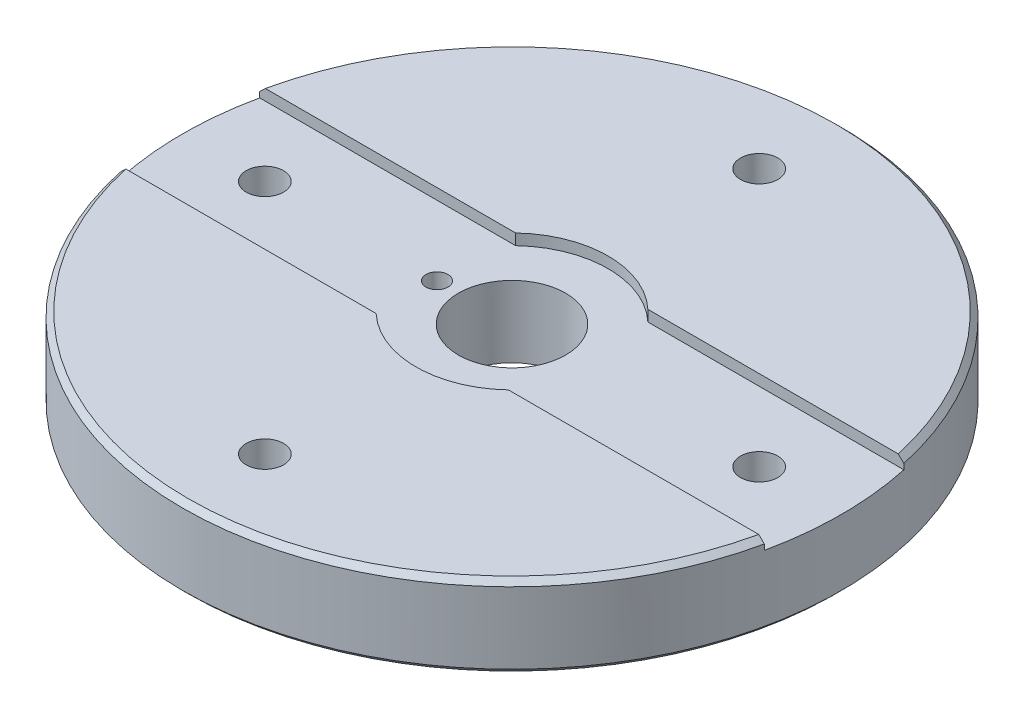
SolidWorks part; units mm, degrees
material "Plain Carbon Steel"
ref_plane "Front Plane" through (0, 0, 0) normal (0, 0, 1) x (1, 0, 0)
ref_plane "Top Plane" through (0, 0, 0) normal (0, 1, 0) x (1, 0, 0)
ref_plane "Right Plane" through (0, 0, 0) normal (1, 0, 0) x (0, 0, -1)
sketch "Sketch1" plane through (0, 0, 0) normal (0, 1, 0) x (1, 0, 0)
  circle A0 centre (0, 0) radius 60
  circle A1 centre (0, 0) radius 9.765
  dimension "D1" = 120
  dimension "D2" = 19.53
extrude "Boss-Extrude1" add sketch "Sketch1" against normal blind 15
chamfer "Chamfer1" distance 1 angle 45 2 edges at (0, -15, 60) (0, 0, 60)
hole_wizard "M8 Tapped Hole1" positions "Sketch6" profile "Sketch3" tap size "M8" standard "ISO" end condition through all
sketch "Sketch6" plane through (0, 0, 0) normal (0, 1, 0) x (1, 0, 0)
  line L0 (0, -45) -> (0, 45) construction
  line L2 (-45, 0) -> (45, 0) construction
  circle A0 centre (0, 0) radius 45
  point P10 (0, -45)
  point P11 (0, 45)
  point P14 (-45, 0)
  point P15 (45, 0)
  point P59 (0, 45)
  point P61 (45, 0)
  point P63 (0, -45)
  point P65 (-45, 0)
  dimension "D1" = 90
sketch "Sketch3" plane through (-45, 0, 0) normal (1, 0, 0) x (0, 0, 1)
  line L0 (0, 0) -> (0, 15)
  line L1 (0, 15) -> (3.4, 15)
  line L2 (3.4, 15) -> (3.4, 0)
  line L5 (3.4, 0) -> (0, 0)
  line L11 (0, -6.35) -> (0, 107.95) construction
  dimension "Thru Tap Drill Dia." = 6.8
  dimension "Thru Tap Drill Depth" = 15
cosmetic thread "Hole Thread1" parameters "D2"=8
cosmetic thread "Hole Thread2" parameters "D2"=8
cosmetic thread "Hole Thread3" parameters "D2"=8
cosmetic thread "Hole Thread4" parameters "D2"=8
sketch "Sketch5" plane through (0, -15, 0) normal (0, -1, 0) x (1, 0, 0)
  line L0 (0, 0) -> (0, 45) construction
  circle A0 centre (0, 0) radius 45 construction
  circle A1 centre (0, 45) radius 10
  dimension "D1" = 0
  dimension "D2" = 20
extrude "Cut-Extrude1" cut sketch "Sketch5" against normal blind 3 contours A1
pattern_circular "CirPattern1" count 12 every 30 about axis through (0, -15, 0) along (0, -1, 0) of "Cut-Extrude1"
sketch "Sketch7" plane through (0, 0, 0) normal (0, 1, 0) x (1, 0, 0)
  line L1 (-60, -12.7) -> (60, -12.7)
  line L2 (-60, -12.7) -> (-60, 12.7)
  line L3 (-60, 12.7) -> (60, 12.7)
  line L4 (60, -12.7) -> (60, 12.7)
  line L5 (-60, -12.7) -> (60, 12.7) construction
  line L6 (-60, 12.7) -> (60, -12.7) construction
  circle A0 centre (0, 0) radius 60 construction
  point P0 (0, 0)
  dimension "D1" = 25.4
extrude "Cut-Extrude2" cut sketch "Sketch7" against normal blind 2 contours L3 L4 L1 L2
sketch "Sketch8" plane through (0, 0, 0) normal (0, 1, 0) x (1, 0, 0)
  circle A0 centre (-13.665, 0) radius 2
  dimension "D1" = 13.665
  dimension "D2" = 4
extrude "Cut-Extrude3" cut sketch "Sketch8" against normal up to next and the other way through all
sketch "Sketch9" plane through (0, 0, 0) normal (0, 1, 0) x (1, 0, 0)
  circle A0 centre (0, 0) radius 17.5
  dimension "D1" = 35
extrude "Cut-Extrude4" cut sketch "Sketch9" against normal up to surface (2 mm away) up to face at (-13.665, -2, -2)
